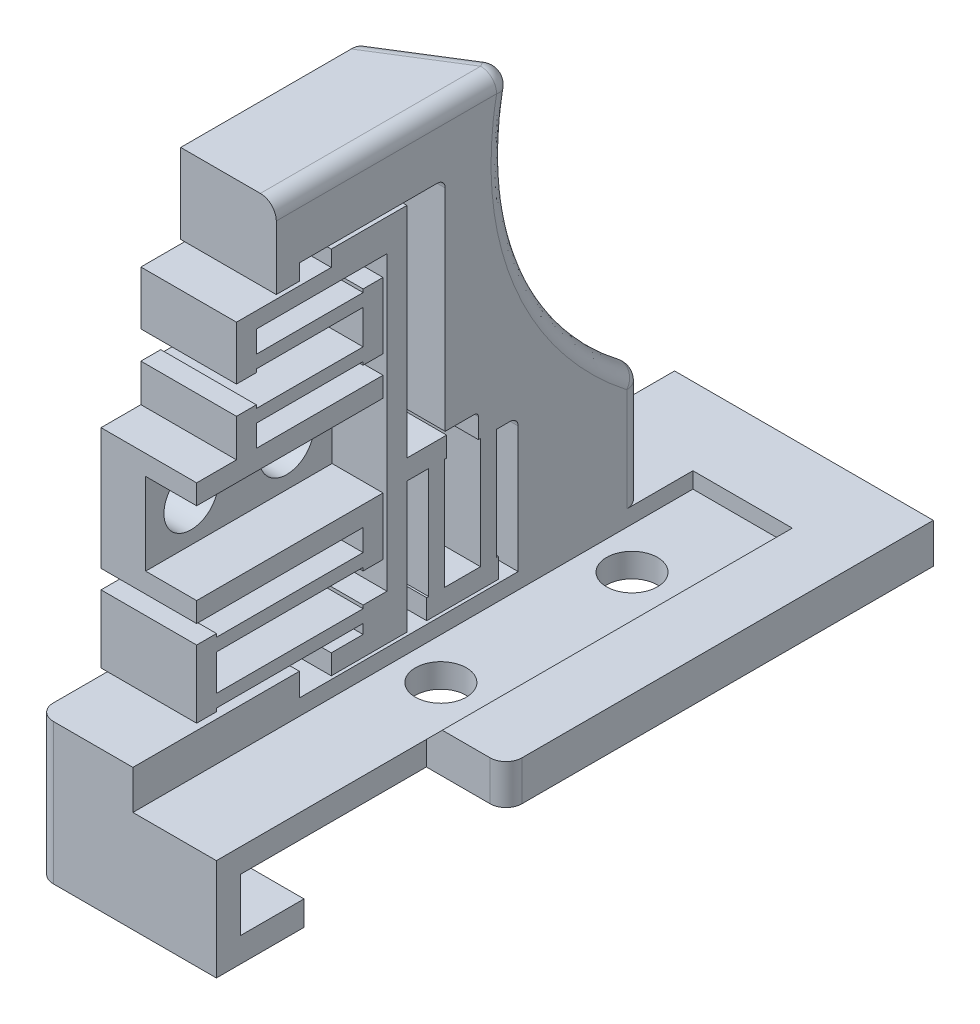
SolidWorks part; units mm, degrees
other "Markup1"
sketch "Sketch8" plane through (10.5, 0, 3) normal (0.7095, 0.0467, 0.7031) x (0.7044, -0.0184, -0.7096)
ref_plane "Front Plane" through (0, 0, 0) normal (0, 0, 1) x (1, 0, 0)
ref_plane "Top Plane" through (0, 0, 0) normal (0, 1, 0) x (1, 0, 0)
ref_plane "Right Plane" through (0, 0, 0) normal (1, 0, 0) x (0, 0, -1)
sketch "Sketch1" plane through (0, 0, 0) normal (1, 0, 0) x (0, 0, -1)
  line L0 (-1.25, -12.7333) -> (6.7, -12.7333)
  line L1 (6.7, -12.7333) -> (6.7, -22.75)
  line L2 (-5, -12.7333) -> (-5, -20.3833)
  line L3 (-5, -20.3833) -> (5.45, -20.3833)
  line L57 (-3.75, -22.55) -> (-3.75, -24.8)
  line L58 (-3.75, -24.8) -> (5.45, -24.8)
  line L60 (5.45, -20.3833) -> (5.45, -21.75)
  line L62 (-5, -21.55) -> (-5, -25.8)
  line L64 (6.95, -6.25) -> (6.95, -24.6)
  line L65 (-1.25, -11.3667) -> (5.45, -11.3667)
  line L66 (5.45, -10.5667) -> (5.45, -8.4167)
  line L68 (-2.5, -8.6167) -> (-2.5, -5.25)
  line L69 (-1.25, -12.7333) -> (-1.25, -11.3667)
  line L71 (6.7, -11.5667) -> (6.7, -7.4167)
  line L73 (-1.25, -7.6167) -> (-1.25, -6.25)
  line L74 (-1.25, -6.25) -> (6.95, -6.25)
  line L75 (-2.5, -5.25) -> (3.45, -5.25)
  line L79 (5.45, -11.3667) -> (5.45, -11.5667)
  line L80 (5.45, -11.5667) -> (6.7, -11.5667)
  line L85 (5.45, -10.5667) -> (-1.25, -10.5667)
  line L86 (-1.25, -10.5667) -> (-1.25, -10.3667)
  line L87 (-1.25, -10.3667) -> (-2.5, -10.3667)
  line L90 (5.45, -8.4167) -> (-1.25, -8.4167)
  line L91 (-1.25, -8.4167) -> (-1.25, -8.6167)
  line L92 (-1.25, -8.6167) -> (-2.5, -8.6167)
  line L93 (-1.25, -7.6167) -> (5.45, -7.6167)
  line L98 (5.45, -7.6167) -> (5.45, -7.4167)
  line L99 (5.45, -7.4167) -> (6.7, -7.4167)
  line L102 (5.45, -21.75) -> (-3.75, -21.75)
  line L103 (-3.75, -21.75) -> (-3.75, -21.55)
  line L104 (-3.75, -21.55) -> (-5, -21.55)
  line L105 (6.7, -22.75) -> (5.45, -22.75)
  line L106 (5.45, -22.75) -> (5.45, -22.55)
  line L111 (5.45, -22.55) -> (-3.75, -22.55)
  line L115 (5.45, -24.8) -> (5.45, -24.6)
  line L116 (5.45, -24.6) -> (6.95, -24.6)
  line L117 (-5, -25.8) -> (-3.75, -25.8)
  line L118 (-3.75, -25.8) -> (-3.75, -25.6)
  line L119 (-3.75, -25.6) -> (5.45, -25.6)
  line L124 (5.45, -25.6) -> (5.45, -26.2)
  line L126 (5.45, -26.2) -> (3.45, -26.2)
  line L127 (3.45, -26.2) -> (3.45, -27.45)
  line L128 (3.45, -27.45) -> (8.2, -27.45)
  line L130 (12.8167, -26.2) -> (10.5667, -26.2)
  line L131 (10.5667, -26.2) -> (10.5667, -19.2333)
  line L136 (10.5667, -19.2333) -> (10.6917, -19.2333)
  line L141 (12.8167, -19.2333) -> (12.8167, -26.2)
  line L145 (9.5667, -26.2) -> (9.4417, -26.2)
  line L146 (9.5667, -26.2) -> (9.5667, -19.2333)
  line L150 (9.5667, -19.2333) -> (8.2, -19.2333)
  line L153 (8.2, -17.9833) -> (10.6917, -17.9833)
  line L155 (14.6833, -19.2333) -> (13.8167, -19.2333)
  line L160 (13.8167, -19.2333) -> (13.8167, -26.2)
  line L168 (15.1833, -27.7) -> (15.1833, -19.7333)
  line L179 (15.1833, -27.7) -> (1.45, -27.7)
  line L180 (1.45, -27.7) -> (1.45, -26.2)
  line L181 (1.45, -26.2) -> (-9, -26.2)
  line L184 (-9, -30.15) -> (23, -30.15)
  line L187 (23, 0) -> (0, 0)
  line L189 (8.2, -27.45) -> (8.2, -19.2333)
  line L190 (1.45, -5) -> (0, -5)
  line L191 (0, -5) -> (0, 0)
  line L192 (13.9417, -26.2) -> (13.8167, -26.2)
  line L193 (12.4417, -17.7333) -> (10.6, -17.7333)
  line L194 (10.6, -17.7333) -> (10.6, -4.5)
  line L198 (9.4417, -26.2) -> (9.4417, -27.45)
  line L199 (13.9417, -26.2) -> (13.9417, -27.45)
  line L200 (13.9417, -27.45) -> (9.4417, -27.45)
  line L201 (8.2, -17.9833) -> (8.2, -4.25)
  line L203 (12.6917, -19.2333) -> (12.6917, -17.9833)
  line L204 (10.6917, -19.2333) -> (10.6917, -17.9833)
  line L205 (12.6917, -19.2333) -> (12.8167, -19.2333)
  line L212 (-9, -30.15) -> (-9, -26.2)
  line L214 (-2.5, -12.7333) -> (-5, -12.7333)
  line L215 (-2.5, -12.7333) -> (-2.5, -10.3667)
  line L216 (23, 0) -> (23, -30.15)
  line L217 (1.45, -5) -> (1.45, -4)
  line L218 (1.45, -4) -> (10.1, -4)
  line L219 (3.45, -5.25) -> (3.45, -4.25)
  line L220 (3.45, -4.25) -> (8.2, -4.25)
  line L221 (13.8167, -19.2333) -> (15.1833, -19.2333) construction
  arc A4 (14.6833, -19.2333) -> (15.1833, -19.7333) centre (14.6833, -19.7333) cw
  arc A5 (12.6917, -17.9833) -> (12.4417, -17.7333) centre (12.4417, -17.9833) ccw
  arc A6 (10.1, -4) -> (10.6, -4.5) centre (10.1, -4.5) cw
  circle A7 centre (3.85, -16.5583) radius 1.7
  circle A8 centre (-2.15, -16.5583) radius 1.7
  circle A9 centre (-2.15, -16.5583) radius 2.85 construction
  circle A10 centre (3.85, -16.5583) radius 2.85 construction
  point P120 (10.6, -5)
  point P140 (15.1833, -19.2333)
  point P144 (12.6917, -17.7333)
  point P151 (-5, -16.5583)
  point P159 (-1.875, -8.6167)
  dimension "D61" = 0.5
  dimension "D62" = 0.25
  dimension "D66" = 0.5
  dimension "D67" = 3.4
  dimension "D68" = 5.7
  dimension "D3" = 4.25
  dimension "D4" = 0.2
  dimension "D6" = 0.8
  dimension "D9" = 0.8
  dimension "D10" = 1.1667
  dimension "D17" = 0.8
  dimension "D18" = 1.75
  dimension "D21" = 0.8
  dimension "D23" = 1
  dimension "D24" = 0.25
  dimension "D37" = 1.25
  dimension "D40" = 0.25
  dimension "D44" = 1
  dimension "D12" = 7.65
  dimension "D20" = 1.25
  dimension "D26" = 1.25
  dimension "D28" = 0.25
  dimension "D33" = 1.25
  dimension "D49" = 2.4
  dimension "D50" = 0.25
  dimension "D31" = 5
  dimension "D54" = 5
  dimension "D55" = 1.25
  dimension "D65" = 2.5
  dimension "D64" = 2.5
  dimension "D29" = 2
  dimension "D52" = 0.25
  dimension "D56" = 1
  dimension "D69" = 6
  dimension "D39" = 4
  dimension "D51" = 32
  dimension "D22" = 1.1667
  dimension "D53" = 2
  dimension "D19" = 0.2
  dimension "D7" = 0.4
  dimension "D8" = 1.45
  dimension "D11" = 1
  dimension "D13" = 4.5
  dimension "D14" = 2
  dimension "D15" = 30.15
  dimension "D16" = 1.25
  dimension "D25" = 1.25
extrude "Boss-Extrude1" add sketch "Sketch1" along normal blind 6
sketch "Sketch2" plane through (0, 0, 5) normal (0, 0, 1) x (1, 0, 0)
  line L0 (6, -12.7333) -> (6, -20.3833) construction
  line L1 (6, -19.1333) -> (2.8, -19.1333)
  line L2 (6, -19.1333) -> (6, -13.9833)
  line L3 (6, -13.9833) -> (2.8, -13.9833)
  line L4 (2.8, -19.1333) -> (2.8, -13.9833)
  line L5 (6, -12.7333) -> (6, -20.3833) construction
  dimension "D1" = 3.2
  dimension "D2" = 1.25
  dimension "D3" = 1.25
extrude "Cut-Extrude4" cut sketch "Sketch2" against normal up to next
sketch "Sketch3" plane through (0, -30.15, 0) normal (0, -1, 0) x (1, 0, 0)
  line L0 (11.24, -4.18) -> (16.24, -4.18)
  line L1 (0, -31) -> (16.24, -31)
  line L2 (0, -31) -> (0, 9)
  line L4 (11.24, -4.18) -> (11.24, 9)
  line L5 (6, 9) -> (6, -23) construction
  line L7 (16.24, -31) -> (16.24, -4.18)
  line L8 (0, 9) -> (0, -23) construction
  line L9 (11.24, 9) -> (0, 9)
  circle A0 centre (8.6, -7.73) radius 1.6
  circle A1 centre (8.6, -19.73) radius 1.6
  dimension "D3" = 3.2
  dimension "D1" = 13.18
  dimension "D2" = 2.6
  dimension "D4" = 12
  dimension "D5" = 5
  dimension "D6" = 40
  dimension "D7" = 16.73
  dimension "D8" = 11.24
sketch "Sketch7" plane through (0, 0, 0) normal (-1, 0, 0) x (0, 0, 1)
  line L0 (2.5, -12.7333) -> (5, -12.7333) construction
  line L2 (-6.7, -12.7333) -> (-6.7, -22.75) construction
  circle A0 centre (2.15, -16.6083) radius 1.7
  circle A1 centre (-3.85, -16.6083) radius 1.7
  circle A2 centre (2.15, -16.6083) radius 2.85 construction
  circle A3 centre (-3.85, -16.6083) radius 2.85 construction
  dimension "D1" = 3.4
  dimension "D2" = 3.875
  dimension "D5" = 5.7
  dimension "D3" = 6
extrude "Cut-Extrude3" cut sketch "Sketch7" against normal up to next
extrude "Boss-Extrude2" add sketch "Sketch3" against normal blind 2.5
sketch "Sketch12" plane through (0, 0, 9) normal (0, 0, 1) x (1, 0, 0)
  line L0 (6, -26.2) -> (6, -27.65) construction
  line L1 (11.24, -27.65) -> (6, -27.65)
  line L2 (11.24, -27.65) -> (11.24, -28.65)
  line L3 (11.24, -28.65) -> (6, -28.65)
  line L4 (6, -27.65) -> (6, -28.65)
  line L5 (11.24, -27.65) -> (6, -27.65) construction
  dimension "D1" = 1
  dimension "D2" = 5.24
extrude "Cut-Extrude6" cut sketch "Sketch12" against normal blind 35.15
sketch "Sketch14" plane through (0, 0, 0) normal (-1, 0, 0) x (0, 0, 1)
  line L1 (9, -28.7) -> (3.5, -28.7)
  line L2 (9, -28.7) -> (9, -35.03)
  line L3 (9, -35.03) -> (3.5, -35.03)
  line L4 (3.5, -28.7) -> (3.5, -35.03)
  line L5 (-1.45, -26.2) -> (9, -26.2) construction
  line L6 (9, -26.2) -> (9, -30.15) construction
  dimension "D1" = 2.5
  dimension "D2" = 6.33
  dimension "D3" = 5.5
extrude "Boss-Extrude4" add sketch "Sketch14" against normal blind 11.24
sketch "Sketch15" plane through (11.24, 0, 0) normal (1, 0, 0) x (0, 0, -1)
  line L1 (-3.5, -30.15) -> (-7.5, -30.15)
  line L2 (-3.5, -30.15) -> (-3.5, -33.48)
  line L3 (-3.5, -33.48) -> (-7.5, -33.48)
  line L4 (-7.5, -30.15) -> (-7.5, -33.48)
  dimension "D1" = 4
  dimension "D2" = 3.33
extrude "Cut-Extrude7" cut sketch "Sketch15" against normal blind 10.25
ref_plane "Plane2" through (0, 0, 7.1) normal (0, 0, 1) x (1, 0, 0)
ref_axis "Axis1" through (11.24, 27.1504, 7.1) along (0, -1, 0)
mirror "Mirror1" [suppressed] of bodies 111
delete or keep bodies "Body-Delete/Keep 1" [suppressed] type delete bodies bodies 111
ref_plane "Plane1" through (4.8929, 0, -3.0574) normal (-0.848, 0, 0.5299) x (0, -1, 0)
sketch "Sketch10" plane through (4.8929, 0, -3.0574) normal (-0.848, 0, 0.5299) x (0, -1, 0)
  line L0 (30.15, 13.5887) -> (30.15, 7.6324) construction
  line L1 (30.15, 2.9682) -> (30.15, -26.2895) construction
  line L2 (30.15, 12.3167) -> (30.15, -33.4435) construction
  circle A0 centre (4.65, -31.2799) radius 21.5
  dimension "D2" = 43
  dimension "D1" = 43.5966
  dimension "D3" = 25.5
extrude "Cut-Extrude5" cut sketch "Sketch10" against normal blind 25
fillet "Fillet1" radius 1 9 edges at (3.1138, -21.4436, -23) (3, 0, -14.0069) (6, -23.8736, -23) (6, -10.8352, -16.3532) (6, 0, -7.9408) (16.24, -28.9, -4.18) (0.99, -31.815, 7.5) (0, -30.615, 9) (0.495, -30.15, 3.5)
chamfer "Chamfer1" distance 1 angle 45 1 edges at (11.24, -27.65, -15.165)
mirror "Mirror2" [suppressed] of bodies 113
delete or keep bodies "Body-Delete/Keep 2" [suppressed] type delete bodies bodies 113
equation "\"VerticalFlexureWidth\"= 0.8"
equation "\"VerticalFlexureGap\"= 1"
equation "\"VerticalDoubleFlexureWidth\"= 2 * \"VerticalFlexureWidth\" + \"VerticalFlexureGap\""
equation "\"HorizontalFlexureLength\"= 7"
equation "\"FlexureJointWidth\"= 1.25"
equation "\"HeadHeight\"= 7.5"
equation "\"VerticalFlexureLength\"= 18"
equation "\"MinGap\"=0.25"
equation "\"BaseplateHeight+Tolerance\"= 3.33"
equation "\"HeadWidth\"= 13"
equation "\"HorizontalFlexureWidth\"= 1"
equation "\"HorizontalFlexureGap\"= 1"
equation "\"HorizontalDoubleFlexureWidth\"= 2 * \"HorizontalFlexureWidth\" + \"HorizontalFlexureGap\""
equation "\"FlexureWidth\"=0.85"
equation "\"FlexureWideWidth\"= 1.25"
equation "\"FlexureGap\"=1.75"
equation "\"TwinFlexureWidth\"= \"FlexureGap\" + 2 * \"FlexureWideWidth\""
equation "\"D3@Sketch1\"=\"TwinFlexureWidth\""
equation "\"FlexureNeckWidth\"= ( \"FlexureWideWidth\" - \"FlexureWidth\" ) / 2"
equation "\"D4@Sketch1\"=\"FlexureNeckWidth\""
equation "\"D6@Sketch1\"=\"VerticalFlexureWidth\""
equation "\"D9@Sketch1\"=\"VerticalFlexureWidth\""
equation "\"D10@Sketch1\"=\"FlexureGapEdge\""
equation "\"D21@Sketch1\"=\"VerticalFlexureWidth\""
equation "\"D18@Sketch1\"=\"FlexureGap\""
equation "\"FlexureLength\"= 2"
equation "\"MainSupport\"=1.5"
equation "\"D24@Sketch1\"=\"MinGap\""
equation "\"D37@Sketch1\"=\"FlexureJointWidth\""
equation "\"D40@Sketch1\"=\"MinGap\""
equation "\"D44@Sketch1\"=\"HorizontalFlexureWidth\""
equation "\"D20@Sketch1\"=\"MainSupport\"-0.25"
equation "\"D26@Sketch1\"=\"FlexureJointWidth\""
equation "\"D28@Sketch1\"=\"MinGap\""
equation "\"D33@Sketch1\"=\"FlexureJointWidth\""
equation "\"FlexureGapEdge\"= \"FlexureGap\" * ( 2 / 3 )"
equation "\"D55@Sketch1\"=\"FlexureJointWidth\""
equation "\"FlexurePlateConnectionHeigh\"= 5.15 + 2.5"
equation "\"D12@Sketch1\"=\"FlexurePlateConnectionHeigh\""
equation "\"D52@Sketch1\"=\"MinGap\""
equation "\"D17@Sketch1\"=\"VerticalFlexureWidth\""
equation "\"D22@Sketch1\"=\"FlexureGapEdge\""
equation "\"D19@Sketch1\"=\"FlexureNeckWidth\""
equation "\"D11@Sketch1\"=\"HorizontalFlexureWidth\""
equation "\"D16@Sketch1\"=\"FlexureJointWidth\""
equation "\"D25@Sketch1\"=\"FlexureJointWidth\""
